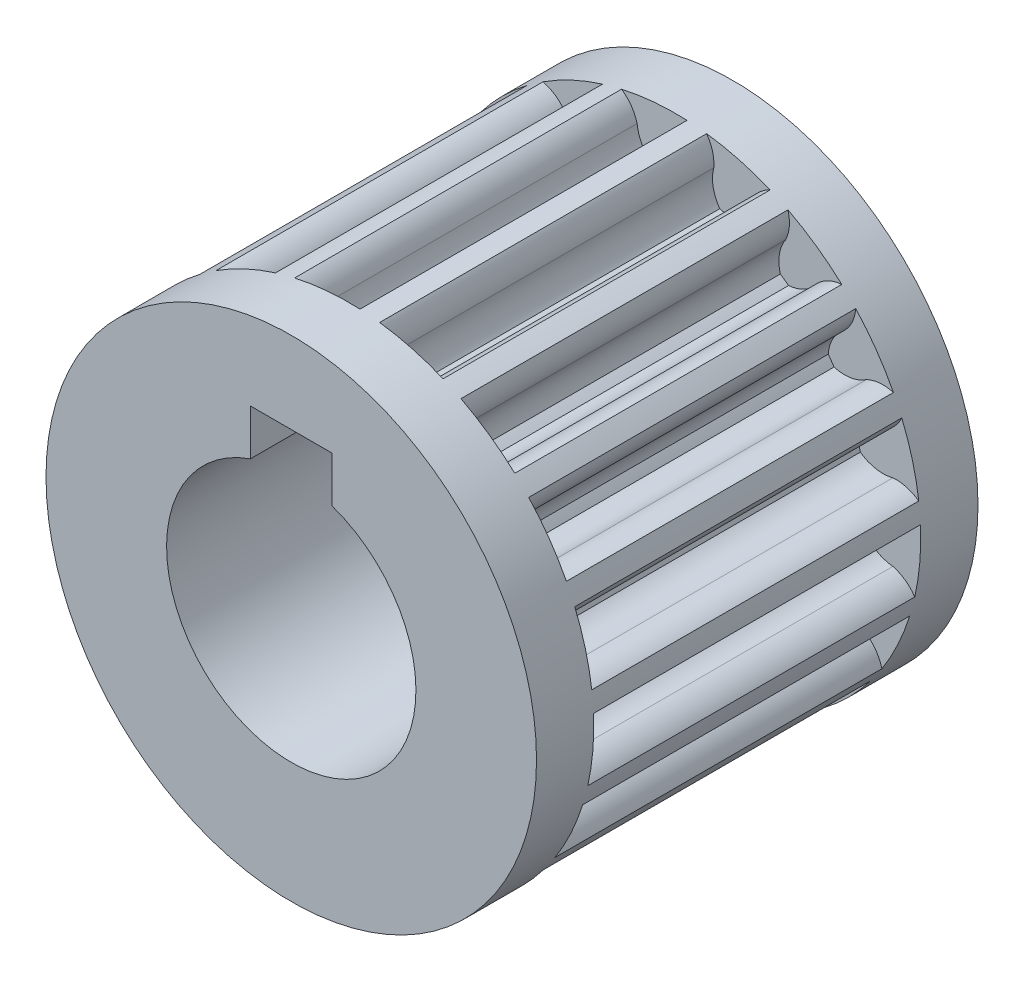
SolidWorks part; units mm, degrees
ref_plane "Alzado" through (0, 0, 0) normal (0, 0, 1) x (1, 0, 0)
ref_plane "Planta" through (0, 0, 0) normal (0, 1, 0) x (1, 0, 0)
ref_plane "Vista lateral" through (0, 0, 0) normal (1, 0, 0) x (0, 0, -1)
sketch "Croquis1" plane through (0, 0, 0) normal (0, 0, 1) x (1, 0, 0)
  arc A6 (0.7063, -11.6035) -> (1.322, -11.5496) centre (0, 0) ccw
  arc A10 (2.3472, -13.2944) -> (3.2988, -14.6328) centre (4.6229, -12.6838) ccw construction
  arc A12 (2.3472, -13.2944) -> (1.322, -11.5496) centre (0, -13.5) ccw construction
  arc A14 (0.7063, -11.6035) -> (0, -13.5) centre (2.3472, -13.2944) ccw construction
  circle A15 centre (0, 0) radius 15
  arc A16 (-0.7044, -14.9835) -> (0, -13.5) centre (-2.3472, -13.2944) ccw construction
  dimension "D1" = 23.25
  dimension "D5" = 4.7124
extrude "Saliente-Extruir1" add sketch "Croquis1" along normal blind 20 contours A15 region at (0, 0, 0)
sketch "Croquis2" plane through (0, 0, 20) normal (0, 0, 1) x (1, 0, 0)
  arc A0 (0.7063, -11.6035) -> (0, -13.5) centre (2.3472, -13.2944) ccw construction
  arc A1 (0.7063, -11.6035) -> (0, -13.5) centre (2.3472, -13.2944) ccw
  arc A2 (-0.7044, -14.9835) -> (0, -13.5) centre (-2.3472, -13.2944) ccw construction
  arc A3 (-0.7044, -14.9835) -> (0, -13.5) centre (-2.3472, -13.2944) ccw
  arc A4 (2.3472, -13.2944) -> (3.2988, -14.6328) centre (4.6229, -12.6838) ccw construction
  arc A5 (2.3472, -13.2944) -> (1.322, -11.5496) centre (0, -13.5) ccw construction
  arc A6 (0.7063, -11.6035) -> (1.322, -11.5496) centre (0, 0) ccw construction
  arc A7 (2.3472, -13.2944) -> (3.2988, -14.6328) centre (4.6229, -12.6838) ccw
  arc A8 (2.3472, -13.2944) -> (1.322, -11.5496) centre (0, -13.5) ccw
  arc A9 (0.7063, -11.6035) -> (1.322, -11.5496) centre (0, 0) ccw
  circle A10 centre (0, 0) radius 15 construction
  arc A11 (-0.7044, -14.9835) -> (3.2988, -14.6328) centre (0, 0) ccw
extrude "Cortar-Extruir1" cut sketch "Croquis2" against normal blind 50
pattern_circular "MatrizC1" count 18 over 360 about axis through (0, 0, 20) along (0, 0, 1) of "Cortar-Extruir1"
sketch "Croquis3" plane through (0, 0, 20) normal (0, 0, 1) x (1, 0, 0)
  line L0 (0, 0) -> (0, 10.0055) construction
  line L1 (-2.5, 7.2035) -> (-2.5, 10.0055)
  line L2 (-2.5, 10.0055) -> (2.5, 10.0055)
  line L3 (2.5, 10.0055) -> (2.5, 7.2035)
  circle A0 centre (0, 0) radius 11.625 construction
  arc A1 (-2.5, 7.2035) -> (2.5, 7.2035) centre (0, 0) ccw
  arc A2 (-4.6323, 10.6622) -> (-5.1924, 10.4009) centre (0, 0) ccw construction
  dimension "D4" = 7.625
  dimension "D2" = 5
  dimension "D3" = 2.802
extrude "Cortar-Extruir2" cut sketch "Croquis3" against normal blind 50
sketch "Croquis4" plane through (0, 0, 0) normal (0, 0, -1) x (-1, 0, 0)
  line L0 (-2.5, 10.0055) -> (2.5, 10.0055) construction
  line L1 (-2.5, 7.2035) -> (-2.5, 10.0055) construction
  line L2 (2.5, 10.0055) -> (2.5, 7.2035) construction
  line L3 (2.5, 10.0055) -> (2.5, 7.2035)
  line L4 (-2.5, 7.2035) -> (-2.5, 10.0055)
  line L5 (-2.5, 10.0055) -> (2.5, 10.0055)
  circle A0 centre (0, 0) radius 15
  arc A1 (-2.5, 7.2035) -> (2.5, 7.2035) centre (0, 0) ccw construction
  arc A2 (-2.5, 7.2035) -> (2.5, 7.2035) centre (0, 0) ccw
  dimension "D1" = 30
extrude "Saliente-Extruir2" add sketch "Croquis4" along normal blind 3.5
sketch "Croquis5" plane through (0, 0, 20) normal (0, 0, 1) x (1, 0, 0)
  line L0 (2.5, 10.0055) -> (2.5, 7.2035) construction
  line L1 (-2.5, 7.2035) -> (-2.5, 10.0055) construction
  line L2 (-2.5, 10.0055) -> (2.5, 10.0055) construction
  line L3 (2.5, 10.0055) -> (2.5, 7.2035)
  line L4 (-2.5, 7.2035) -> (-2.5, 10.0055)
  line L5 (-2.5, 10.0055) -> (2.5, 10.0055)
  arc A0 (-2.5, 7.2035) -> (2.5, 7.2035) centre (0, 0) ccw construction
  circle A1 centre (0, 0) radius 15
  circle A2 centre (0, 0) radius 15
  arc A3 (-2.5, 7.2035) -> (2.5, 7.2035) centre (0, 0) ccw
  dimension "D1" = 0
extrude "Saliente-Extruir3" add sketch "Croquis5" along normal blind 3.5
